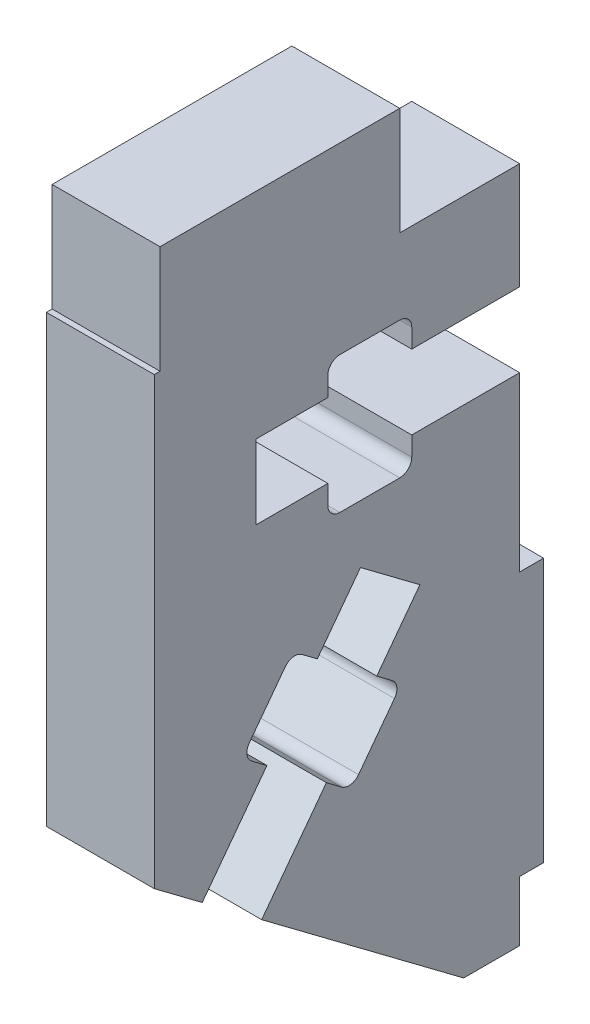
SolidWorks part; units mm, degrees
ref_plane "Front Plane" through (0, 0, 0) normal (0, 0, 1) x (1, 0, 0)
ref_plane "Top Plane" through (0, 0, 0) normal (0, 1, 0) x (1, 0, 0)
ref_plane "Right Plane" through (0, 0, 0) normal (1, 0, 0) x (0, 0, -1)
sketch "Sketch1" plane through (0, 0, 0) normal (1, 0, 0) x (0, 0, -1)
  line L0 (0, 0) -> (0, -30)
  line L1 (0, -30) -> (-40, 0)
  line L2 (-40, 0) -> (0, 0)
  dimension "D1" = 40
  dimension "D2" = 30
extrude "Boss-Extrude1" add sketch "Sketch1" along normal blind 4.5
sketch "Sketch2" plane through (4.5, 0, 0) normal (1, 0, 0) x (0, 0, -1)
  line L0 (0, -25.75) -> (1, -25.75)
  line L1 (0, -30) -> (0, 0) construction
  line L2 (1, -25.75) -> (1, -14.75)
  line L3 (1, -14.75) -> (0, -14.75)
  line L4 (0, -14.75) -> (0, -25.75)
  line L5 (1, -20.25) -> (0, -20.25) construction
  line L6 (0, -14.75) -> (4.5, -14.75) construction
  line L7 (0, -25.75) -> (4.5, -25.75) construction
  dimension "D1" = 0
  dimension "D2" = 1
  dimension "D3" = 0
extrude "Boss-Extrude2" add sketch "Sketch2" against normal through all
sketch "Sketch3" plane through (4.5, 0, 0) normal (1, 0, 0) x (0, 0, -1)
  line L0 (0, -6) -> (-11, -6) construction
  line L1 (0, -14.75) -> (0, 0) construction
  line L2 (-11, -7.55) -> (-11, -4.45) construction
  line L3 (-11, -4.45) -> (0, -4.45) construction
  line L4 (0, -4.45) -> (-4.5, -4.45)
  line L5 (-4.5, -4.45) -> (-4.5, -3.65)
  line L6 (-5, -3.15) -> (-7.5, -3.15)
  line L7 (-8, -3.65) -> (-8, -4.45)
  line L8 (-8, -4.45) -> (-11, -4.45)
  line L9 (-11, -4.45) -> (-11, -7.55)
  line L10 (0, -4.45) -> (0, -7.55)
  line L12 (-11, -7.55) -> (0, -7.55) construction
  line L13 (-8, -7.55) -> (-11, -7.55)
  line L14 (-8, -8.35) -> (-8, -7.55)
  line L15 (-5, -8.85) -> (-7.5, -8.85)
  line L16 (-4.5, -7.55) -> (-4.5, -8.35)
  line L17 (0, -7.55) -> (-4.5, -7.55)
  arc A0 (-4.5, -3.65) -> (-5, -3.15) centre (-5, -3.65) ccw
  arc A1 (-7.5, -3.15) -> (-8, -3.65) centre (-7.5, -3.65) ccw
  arc A2 (-7.5, -8.85) -> (-8, -8.35) centre (-7.5, -8.35) cw
  arc A3 (-4.5, -8.35) -> (-5, -8.85) centre (-5, -8.35) cw
  point P15 (-4.5, -3.15)
  point P18 (-8, -3.15)
  point P29 (-8, -8.85)
  point P30 (-4.5, -8.85)
  dimension "D7" = 0.5
  dimension "D1" = 11
  dimension "D2" = 1.55
  dimension "D3" = 3.5
  dimension "D4" = 2.85
  dimension "D5" = 8
  dimension "D6" = 6
extrude "Cut-Extrude1" cut sketch "Sketch3" against normal through all
sketch "Sketch4" plane through (4.5, 0, 0) normal (1, 0, 0) x (0, 0, -1)
  line L0 (-13.24, -20.07) -> (-6.64, -11.27) construction
  line L1 (-40, 0) -> (0, -30) construction
  line L2 (-6.64, -11.27) -> (-4.16, -13.13) construction
  line L3 (-5.4, -12.2) -> (-12, -21) construction
  line L4 (-10.76, -21.93) -> (-13.24, -20.07)
  line L5 (-13.24, -20.07) -> (-10.54, -16.47)
  line L6 (-10.54, -16.47) -> (-11.18, -15.99)
  line L7 (-11.28, -15.29) -> (-9.78, -13.29)
  line L8 (-9.08, -13.19) -> (-8.44, -13.67)
  line L9 (-8.44, -13.67) -> (-6.64, -11.27)
  line L10 (-6.64, -11.27) -> (-4.16, -13.13)
  line L11 (0, 0) -> (-40, 0) construction
  line L12 (-10.76, -21.93) -> (-4.16, -13.13) construction
  line L13 (-5.96, -15.53) -> (-4.16, -13.13)
  line L14 (-5.32, -16.01) -> (-5.96, -15.53)
  line L15 (-6.72, -18.71) -> (-5.22, -16.71)
  line L16 (-8.06, -18.33) -> (-7.42, -18.81)
  line L17 (-10.76, -21.93) -> (-8.06, -18.33)
  arc A0 (-11.18, -15.99) -> (-11.28, -15.29) centre (-10.88, -15.59) cw
  arc A1 (-9.78, -13.29) -> (-9.08, -13.19) centre (-9.38, -13.59) cw
  arc A2 (-5.22, -16.71) -> (-5.32, -16.01) centre (-5.62, -16.41) ccw
  arc A3 (-7.42, -18.81) -> (-6.72, -18.71) centre (-7.12, -18.41) ccw
  point P14 (-11.58, -15.69)
  point P17 (-9.48, -12.89)
  point P28 (-4.92, -16.31)
  point P29 (-7.02, -19.11)
  dimension "D7" = 0.5
  dimension "D1" = 11
  dimension "D2" = 1.55
  dimension "D3" = 3.5
  dimension "D4" = 2.85
  dimension "D5" = 8
  dimension "D6" = 21
extrude "Cut-Extrude2" cut sketch "Sketch4" against normal through all
sketch "Sketch5" plane through (4.5, 0, 0) normal (1, 0, 0) x (0, 0, -1)
  line L0 (-15.24, -18.57) -> (-15.24, 0)
  line L1 (-40, 0) -> (-13.24, -20.07) construction
  line L2 (0, 0) -> (-40, 0) construction
  line L3 (-15.24, 0) -> (-40, 0)
  line L4 (-40, 0) -> (-15.24, -18.57)
  dimension "D1" = 2
extrude "Cut-Extrude3" cut sketch "Sketch5" against normal through all
sketch "Sketch6" plane through (0, 0, 11) normal (0, 0, -1) x (-1, 0, 0)
  line L0 (-2.25, -4.45) -> (-2.25, -7.55) construction
  line L1 (0, -4.45) -> (-4.5, -4.45) construction
  line L2 (0, -7.55) -> (-4.5, -7.55) construction
  circle A0 centre (-2.25, -6) radius 1.5
  dimension "D1" = 3
sketch "Sketch7" plane through (0, -10.4, 7.8) normal (0, -0.8, 0.6) x (1, 0, 0)
  line L0 (2.25, -1.45) -> (2.25, -4.55) construction
  line L1 (0, -1.45) -> (4.5, -1.45) construction
  line L2 (0, -4.55) -> (4.5, -4.55) construction
  circle A0 centre (2.25, -3) radius 1.55
sketch "Sketch8" plane through (4.5, 0, 0) normal (1, 0, 0) x (0, 0, -1)
  line L0 (-10, 4.5) -> (-10, 0) construction
  line L1 (-15, 0) -> (-5, 0)
  line L2 (-15, 0) -> (-15, 4.5)
  line L3 (-15, 4.5) -> (-5, 4.5)
  line L4 (-5, 0) -> (-5, 4.5)
  line L5 (0, 0) -> (-15.24, 0) construction
  dimension "D1" = 10
  dimension "D2" = 4.5
  dimension "D3" = 10
extrude "Boss-Extrude3" add sketch "Sketch8" against normal through all
sketch "Sketch10" plane through (4.5, 0, 0) normal (1, 0, 0) x (0, 0, -1)
  line L0 (0, -28.25) -> (-2.3333, -28.25)
  line L1 (0, -30) -> (0, -25.75) construction
  line L2 (-10.76, -21.93) -> (0, -30) construction
  line L3 (-2.3333, -28.25) -> (0, -30)
  line L4 (0, -30) -> (0, -28.25)
  dimension "D1" = 0
extrude "Cut-Extrude4" cut sketch "Sketch10" against normal through all contours L0 L3 L4
equation "\"X-ROD-SPACING\"=45"
equation "\"Y-ROD-SPACING\"=75"
equation "\"Z-ROD-SPACING\"=17.5"
equation "\"Y-BED-OFFSET\"=2"
equation "\"Y-BED-ROD-INSET\"=3.5"
equation "\"Y-BED-SCREW-SPACING\"=209"
equation "\"Y-BED-SCREW-CUTOUT-SLOT-HEIGHT\"=2"
equation "\"T-SLOT-NUT-FILLET-RADIUS\"=0.5"
equation "\"T-SLOT-SCREW-SHAFT-RADIUS\"=1.55"
equation "\"T-SLOT-SCREW-SHAFT-CUTOUT-LENGTH\"=11"
equation "\"T-SLOT-NUT-DEPTH\"=3.5"
equation "\"T-SLOT-NUT-WIDTH\"=2.85"
equation "\"T-SLOT-NUT-END-DISTANCE\"=8"
equation "\"ACRYLIC-THICKNESS\"=10"
equation "\"ACRYLIC-THICKNESS2\"=4.5"
equation "\"ACRYLIC-TAB-CUTOUT-SIZE\"=\"ACRYLIC-THICKNESS\"+\"ACRYLIC-TAB-TOLERANCE\"*2"
equation "\"ACRYLIC-TAB-TOLERANCE\"=-.05"
equation "\"ACRYLIC-TAB-WIDTH\"=\"ACRYLIC-THICKNESS\""
equation "\"ACRYLIC-M3-HOLE\"=2.9"
equation "\"SMOOTHROD-CAP-SCREW-DISTANCE\"=20"
equation "\"FRAME-WIDTH-INNER\"=370"
equation "\"NEMA17-HOLE-SPACING\"=31"
equation "\"NEMA17-CENTRAL-CUTOUT\"=22.5"
equation "\"Z-BRACKET-REACH\"=57"
equation "\"Z-ROD-INSET\"=13.5"
equation "\"TOP-BRACKET-SPACING\"=40"
equation "\"SMOOTHROD-X-LENGTH\"=350"
equation "\"SMOOTHROD-Y-LENGTH\"=350"
equation "\"SMOOTHROD-Z-LENGTH\"=350"
equation "\"SMOOTHROD-TIGHTENING-HEADROOM\"=.25"
equation "\"LEADSCREW-Z-LENGTH\"=300"
equation "\"SCREW-LENGTH-FRAME\"=\"ACRYLIC-THICKNESS\" + 10"
equation "\"SCREW-LENGTH-MOTOR\"=\"ACRYLIC-THICKNESS\" + 5"
equation "\"SCREW-LENGTH-EXTRUDER\"=28"
equation "\"SCREW-HEAD-RADIUS\"=6"
equation "\"PRINTED-M3-HOLE\"=3.5"
equation "\"PRINTED-X-SMOOTHROD-DIAMETER\"=8.8"
equation "\"PRINTED-X-SMOOTHROD-CUTOUT\"=10"
equation "\"PRINTED-X-BASE-HEIGHT\"=10"
equation "\"PRINTED-LM8UU-CUTOUT-SIZE\"=15.5"
equation "\"PRINTED-LM8UU-CUTOUT-LENGTH\"=24.5"
equation "\"PRINTED-X-IDLER-HEIGHT\"=16"
equation "\"PRINTED-M3-NUT-AF\"=6.25"
equation "\"PSU-MOUNTING-WIDTH\"=95"
equation "\"PSU-MOUNTING-HEIGHT\"=177"
equation "\"Y-BELT-TO-ROD-DISTANCE\"=20"
equation "\"SPOOL-HOLDER-ROD-SPACING\"=150"
equation "\"ACRYLIC-X-CARRIAGE-WIDTH\"=55"
equation "\"ACRYLIC-X-CARRIAGE-HEIGHT\"=75"
equation "\"ACRYLIC-X-CARRIAGE-LM8UU-CUTOUT-WIDTH\"=24.25"
equation "\"ACRYLIC-X-CARRIAGE-LM8UU-CUTOUT-HEIGHT\"=11.0"
equation "\"ACRYLIC-X-CARRIAGE-SCREW-SPACING-X\"=15"
equation "\"ACRYLIC-X-CARRIAGE-SCREW-SPACING-Y\"=33"
equation "\"ACRYLIC-X-CARRIAGE-CENTER-TAB-SPACING\"=14"
equation "\"ACRYLIC-X-CARRIAGE-EXTRUDER-OFFSET\"=26"
equation "\"ACRYLIC-X-CARRIAGE-EXTRUDER-ANGLE\"=90"
equation "\"ACRYLIC-X-CARRIAGE-EXTRUDER-SHELF-DEPTH\"=\"ACRYLIC-X-CARRIAGE-EXTRUDER-OFFSET\" + 28"
equation "\"ACRYLIC-X-CARRIAGE-EXTRUDER-BRACE-SPACING\"=23"
equation "\"ACRYLIC-X-CARRIAGE-EXTRUDER-BRACE-TAB-OFFSET\"=20"
equation "\"ACRYLIC-X-CARRIAGE-EXTRUDER-BRACE-HEIGHT\"=35"
equation "\"ACRYLIC-X-CARRIAGE-EXTRUDER-BRACE-SCREW-SPACING\"=22"
equation "\"ACRYLIC-X-CARRIAGE-DUAL-WIDTH-MULTIPLIER\"=1.65"
equation "\"ACRYLIC-X-CARRIAGE-DUAL-HOTEND-SPACING\"=42"
equation "\"ACRYLIC-X-CARRIAGE-DUAL-WIDTH\"=75"
equation "\"ACRYLIC-X-CARRIAGE-DUAL-FAN-OFFSET\"=52"
equation "\"ACRYLIC-X-CARRIAGE-DUAL-FAN-HEIGHT\"=20"
equation "\"ACRYLIC-X-CARRIAGE-DUAL-HOTEND-SEPARATION\"=36"
equation "\"ACRYLIC-X-CARRIAGE-DUAL-MOUNT-PLATE-DEPTH\"=75"
equation "\"ACRYLIC-X-CARRIAGE-DUAL-MOUNT-BRACE-WIDTH\"=33"
equation "\"ACRYLIC-X-CARRIAGE-DUAL-MOUNT-SCREW-WIDTH\"=40"
equation "\"BLOWER-FAN-WIDTH\"=15"
equation "\"D1@Boss-Extrude1\"=\"ACRYLIC-THICKNESS2\""
equation "\"D1@Sketch3\"=\"T-SLOT-SCREW-SHAFT-CUTOUT-LENGTH\""
equation "\"D2@Sketch3\"=\"T-SLOT-SCREW-SHAFT-RADIUS\""
equation "\"D3@Sketch3\"=\"T-SLOT-NUT-DEPTH\""
equation "\"D4@Sketch3\"=\"T-SLOT-NUT-WIDTH\""
equation "\"D5@Sketch3\"=\"T-SLOT-NUT-END-DISTANCE\""
equation "\"D7@Sketch3\"=\"T-SLOT-NUT-FILLET-RADIUS\""
equation "\"D1@Sketch4\"=\"T-SLOT-SCREW-SHAFT-CUTOUT-LENGTH\""
equation "\"D2@Sketch4\"=\"T-SLOT-SCREW-SHAFT-RADIUS\""
equation "\"D3@Sketch4\"=\"T-SLOT-NUT-DEPTH\""
equation "\"D4@Sketch4\"=\"T-SLOT-NUT-WIDTH\""
equation "\"D5@Sketch4\"=\"T-SLOT-NUT-END-DISTANCE\""
equation "\"D7@Sketch4\"=\"T-SLOT-NUT-FILLET-RADIUS\""
equation "\"D1@Sketch8\"=\"ACRYLIC-TAB-WIDTH\""
equation "\"D2@Sketch8\"=\"ACRYLIC-THICKNESS2\""
